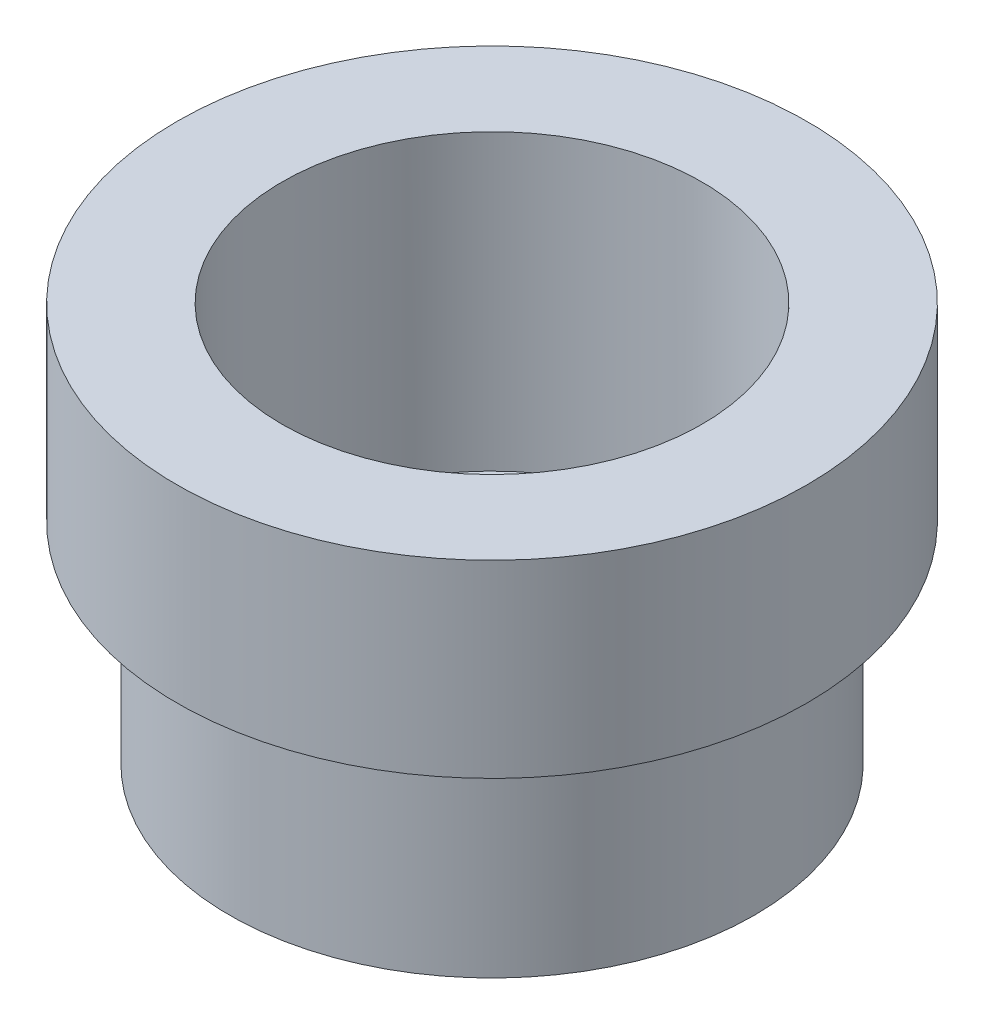
SolidWorks part; units mm, degrees
material "1060 Alloy"
ref_plane "Front" through (0, 0, 0) normal (0, 0, 1) x (1, 0, 0)
ref_plane "Top" through (0, 0, 0) normal (0, 1, 0) x (1, 0, 0)
ref_plane "Right" through (0, 0, 0) normal (1, 0, 0) x (0, 0, -1)
sketch "Sketch1" plane through (0, 0, 0) normal (0, 0, 1) x (1, 0, 0)
  line L0 (0, 0) -> (25, 0)
  line L1 (25, 0) -> (25, 20)
  line L2 (25, 20) -> (30, 20)
  line L3 (30, 20) -> (30, 38)
  line L6 (30, 38) -> (0, 38)
  line L7 (0, 38) -> (0, 0)
  dimension "D1" = 18
  dimension "D2" = 20
  dimension "D3" = 30
  dimension "D4" = 25
revolve "Revolve1" add sketch "Sketch1" angle 360 about L7
sketch "Sketch3" plane through (0, 38, 0) normal (0, 1, 0) x (1, 0, 0)
  circle A0 centre (0, 0) radius 10
  dimension "D1" = 20
extrude "bore through" cut sketch "Sketch3" against normal through all
sketch "Sketch5" plane through (0, 38, 0) normal (0, 1, 0) x (1, 0, 0)
  circle A0 centre (0, 0) radius 20
  dimension "D1" = 40
extrude "center cavity" cut sketch "Sketch5" against normal offset from surface (28 mm away) 10 up to face at (0, 0, 10)
sketch "m4 pattern alignment" plane through (0, 10, 0) normal (0, 1, 0) x (1, 0, 0)
  circle A0 centre (0, 0) radius 15 construction
  point P3 (0, 15)
  point P4 (12.9904, 7.5)
  point P7 (12.9904, -7.5)
  point P8 (0, -15)
  point P9 (-12.9904, -7.5)
  point P10 (-12.9904, 7.5)
  point P11 (0, 0)
  dimension "D1" = 30
  dimension "D2" = 6
hole_wizard "CBORE for M4 SHCS1" positions "Sketch11" profile "Sketch12" counterbore size "M4" standard "ANSI Metric" end condition through all
sketch "Sketch11" plane through (0, 10, 0) normal (0, 1, 0) x (1, 0, 0)
  point P0 (0, 15.0587)
  point P8 (13.0412, 7.5293)
  point P9 (13.0412, -7.5293)
  point P10 (0, -15.0587)
  point P11 (-13.0412, -7.5293)
  point P12 (-13.0412, 7.5293)
  point P13 (0, 0)
  dimension "D1" = 6
sketch "Sketch12" plane through (0, 10, -15.0587) normal (1, 0, 0) x (0, 0, 1)
  line L0 (0, 0) -> (0, 10)
  line L1 (0, 10) -> (2.15, 10)
  line L3 (2.15, 10) -> (2.15, 4)
  line L4 (2.15, 4) -> (4, 4)
  line L5 (4, 4) -> (4, 0)
  line L7 (4, 0) -> (0, 0)
  line L11 (0, -6.35) -> (0, 107.95) construction
  dimension "Thru Hole Dia." = 4.3
  dimension "Thru Hole Depth" = 10
  dimension "C'Bore Dia." = 8
  dimension "C'Bore Depth" = 4
equation "\"D1\"= \"motor mount plate thickness\""
equation "\"coupler motor shaft hole ID\"= 8mm"
equation "\"coupler OD\"= 17mm"
equation "\"coupler length\"= 25mm"
equation "\"square plate bolt pattern diameter\"= 3.5in"
equation "\"motor mount m4 screw hole diameter\"= 4mm"
equation "\"motor mount m4 head diameter\"= 7.25mm"
equation "\"motor mount m4 head depth\"= 4mm"
equation "\"motor mount plate thickness\"= 8mm + \"motor mount m4 head depth\""
equation "\"motor shaft pride\"= 32mm"
equation "\"motor mount m4 pattern diamater\" = 30mm"
equation "\"motor OD\" = 64mm"
equation "\"square plate bolt bore\" = \"m8 clearance\""
equation "\"square plate bolt head diameter\" = 13.5mm"
equation "\"motor to bearing plate distance\" = \"motor shaft pride\" + 2mm +\"coupler length\"/2"
equation "\"motor mount center bore\"= \"coupler OD\"+ 4mm"
equation "\"motor mount post radius\"= ( 3 * \"square plate bolt bore\" ) / 2"
equation "\"motor shaft diameter\"= 8mm"
equation "\"D1\"= 20mm"
equation "\"z\" = 8\t\t\t\t'number of blades"
equation "\"de\" = 0.43in\t\t\t'entrance eye diameter"
equation "\"de_length\" = 4mm\t\t'entrance eye consistent length"
equation "\"d_exit\" = 0.18in \t\t'throat aka d1"
equation "\"d2\" = 2.1in \t\t\t'outer diameter of the impeller"
equation "\"b2\" = .2in\t\t\t'tip height from disc surface at d2; slightly higher than d_exit"
equation "\"theta\" = 12\t\t\t'angle of blades from inner to outer "
equation "\"ae\" = 3.14*(\"de\"^2)/4\t\t'entrance eye area'"
equation "\"ce\" = 3.14*\"de\"\t\t'entrance eye circumference"
equation "\"av_ratio\" = .325\t\t'ratio of av/ae at N_s of 470, range is .275 to .375, .325 ideal. High ratio means bigger area means smaller blades"
equation "\"av\" = \"ae\"*\"av_ratio\"\t\t'area between just two blades"
equation "\"min blade thickness\" = .15in"
equation "\"diffuser cartridge OD\" =.75in"
equation "\"diffuser flange bolt pattern diameter\" = 1.4in"
equation "\"bearing OD\" = 30mm"
equation "\"bearing ID\"= 10mm"
equation "\"bearing depth\"= 9mm"
equation "\"bearing outer race thickness\"= 1mm"
equation "\"bearing inner race thickness\"= 1mm"
equation "\"bearing bore\" = \"bearing depth\" + 1mm"
equation "\"lower seal OD\" = .917in\t\t'this is https://www.mcmaster.com/#9281k121/=174001b"
equation "\"lower seal ID\"= .375in"
equation "\"lower seal depth\" = .625in + .218in"
equation "\"lower seal bore\" = \"lower seal depth\" + 1mm"
equation "\"upper seal OD\" = 1.125in\t'this is https://www.mcmaster.com/#5154t33/=173zuau, needs to be visually inspected before machining!"
equation "\"upper seal ID\"= 0.625in"
equation "\"upper seal depth\"= .25in\t'aka height; these values need to be confirmed by inspection!! We may want to compress the height."
equation "\"upper seal bore\" = \"upper seal depth\" + 1mm"
equation "\"big o-ring thickness\" = .139in"
equation "\"big o-ring OD\" = 2.734in"
equation "\"big o-ring ID\" = 3.012in"
equation "\"big o-ring groove depth\" = \"big o-ring thickness\"*4/5"
equation "\"impeller upper clearance\"= .5mm"
equation "\"impeller horizontal clearance\"= (\"d2\"*1.15 - \"d2\")/2 \t\t'clearance based on D2-D3 ratio for circular volute, ranges 1.15 to 1.2"
equation "\"impeller bottom clearance\"= .5mm"
equation "\"impeller base thickness\"= 2mm"
equation "\"impeller dowel diameter\" = 2mm"
equation "\"impeller bolt head depth\" = 4mm"
equation "\"impeller bolt stop depth\" = 3mm"
equation "\"impeller shaft bore depth\" = 12mm"
equation "\"impeller shaft bore\" = 8mm"
equation "\"impeller boss depth\" = \"impeller shaft bore depth\"+\"impeller bolt stop depth\"+\"impeller bolt head depth\"-\"impeller base thickness\""
equation "\"impeller boss diameter\" = \"upper seal ID\""
equation "\"impeller dowel length\" = 2mm*2 + \"impeller shaft bore\""
equation "\"square plate bolt head depth\" = 8mm"
equation "\"bearing plate stop ID\" = \"bearing OD\" - 4mm"
equation "\"bearing plate stop depth\" = 3mm"
equation "\"lower seal plate lip depth\" = 2mm"
equation "\"lower seal plate lip ID\" = \"lower seal OD\" - 3mm"
equation "\"lower seal plate thickness\" = \"lower seal plate lip depth\" + \"lower seal bore\""
equation "\"shaft coupler section diameter\" = 8mm"
equation "\"shaft coupler section length\" = \"motor to bearing plate distance\" - \"motor shaft pride\" - 2mm"
equation "\"shaft bearing section diameter\" = \"bearing ID\""
equation "\"shaft bearing section length\" = \"bearing plate stop depth\" + \"bearing depth\""
equation "\"shaft bearing stop diameter\" = \"bearing ID\" + 4mm"
equation "\"shaft bearing stop length\" = 3mm"
equation "\"shaft lower seal section diameter\" = \"lower seal ID\""
equation "\"shaft lower seal section length\" = \"lower seal plate thickness\" + 1mm"
equation "\"shaft impeller section diameter\" = \"impeller shaft bore\""
equation "\"upper seal plate lip ID\" = \"upper seal OD\" - 3mm"
equation "\"upper seal plate riser\" = 6.59mm \t\t'this number needs to be read from the housing file"
equation "\"upper seal plate pressure hole diameter\" = .125in\t'this is 1/8 drill "
equation "\"upper seal plate pressure tap diameter\" = .328125in \t'this is 21/64 drill for a 1/8 ANPT tap"
equation "\"upper seal plate pressure tap grip\" = 5mm\t\t'this is the area around the tap so it doesn't crack"
equation "\"upper seal plate pressure tap depth\" = 12mm"
equation "\"impeller cavity diameter\"= 2 * \"impeller horizontal clearance\" + \"d2\" \t\t\t\t\t\t\t\t\t'called D3 analytically"
equation "\"impeller cavity outer height\"= \"impeller bottom clearance\" + \"impeller upper clearance\" + \"impeller base thickness\" + \"b2\" \t\t'this is height at impeller diameter d2, not at d3"
equation "\"impeller housing diameter\" = 4.5in"
equation "\"impeller housing bolt count\" = 8"
equation "\"impeller housing bolt pattern diameter\" = 3.5in"
equation "\"impeller housing threaded inlet diameter\" = 0.71875in \t'this is the 23/32 drill size for 1/2 NPT fitting https://www.mcmaster.com/#50715k269/=176pljy"
equation "\"impeller housing threaded inlet depth\"= .6in"
equation "\"impeller housing exit threaded diameter\"= 0.515625in \t\t'this is the 33/64 drill size for 9/16-18 fitting, expecting swagelok SS-8FK0-1-6STH fitting"
equation "\"impeller housing exit threaded depth\"= 10mm"
equation "\"impeller housing diffuser conical angle\"=10"
equation "\"impeller housing diffuser tangent angle\"=5"
equation "\"impeller housing diffuser final diameter\" = .38in\t\t'aka d2'"
equation "\"impeller housing outlet grip\" = 5mm"
equation "\"end mill size\" = 0.375in\t'for 3/8 endmill"
equation "\"m4 clearance\" = 0.171875in \t'this is 11/64 bit for 4.36mm"
equation "\"m4 tap\" = 0.125in\t\t'this is 1/8 bit for 3.17mm"
equation "\"m4 head bore diameter\" = 7.5mm"
equation "\"m4 head bore depth\" = 5mm\t'actual is ~4mm"
equation "\"m6 clearance\" = 0.234375in\t'this is 15/64 bit = 5.95mm, could use 6mm bit, B bit for 6.04mm or 1/4 bit for 6.35mm"
equation "\"m6 tap\" = 5mm\t\t\t'5mm is appropriate, could use 13/64 or #5,6,7"
equation "\"m6 head bore diameter\" = 11mm\t\t"
equation "\"m6 head bore depth\" = 7mm\t'actual is 6mm"
equation "\"m8 clearance\" = 0.3125in\t'this is 5/16in for 7.93mm, could use 8mm, O,P, or 21/64"
equation "\"m8 tap\" = 0.265625in\t\t'this is 17/64 for 6.746875mm"
equation "\"m8 head bore diameter\" = 14mm"
equation "\"m8 head bore depth\" = 9mm\t'actual is 8mm"
